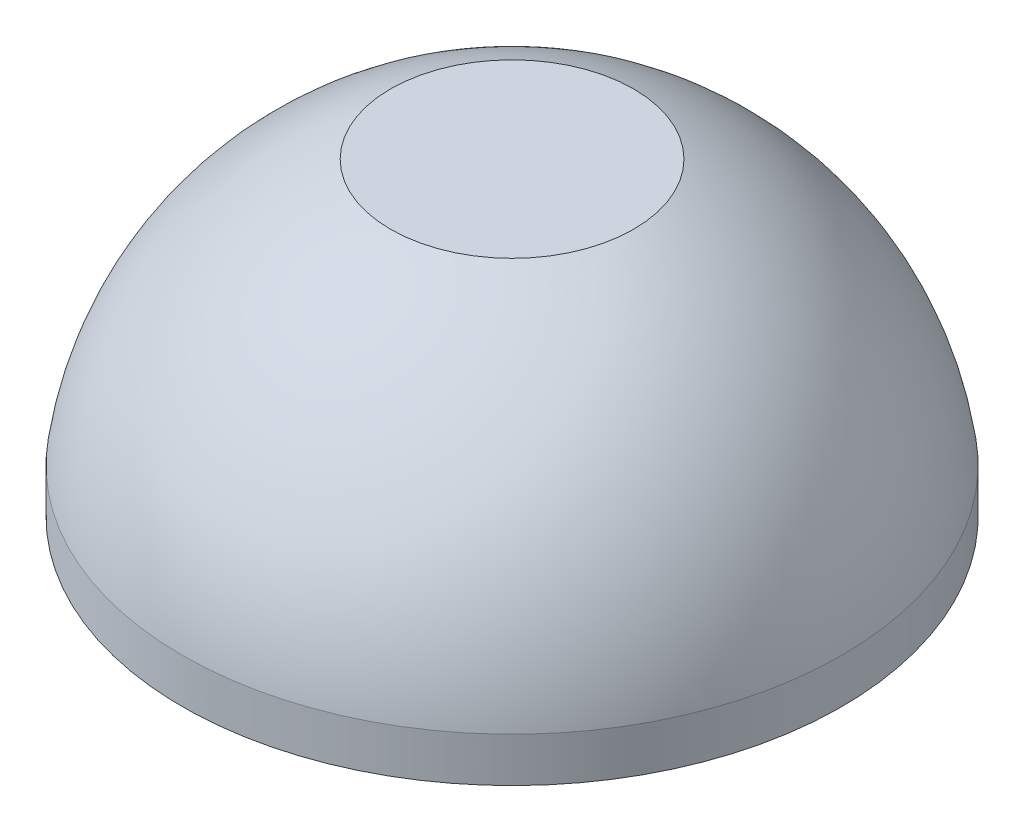
SolidWorks part; units mm, degrees
ref_plane "Front Plane" through (0, 0, 0) normal (0, 0, 1) x (1, 0, 0)
ref_plane "Top Plane" through (0, 0, 0) normal (0, 1, 0) x (1, 0, 0)
ref_plane "Right Plane" through (0, 0, 0) normal (1, 0, 0) x (0, 0, -1)
sketch "Sketch2" plane through (0, 0, 0) normal (0, 0, 1) x (1, 0, 0)
  line L0 (0, 70.1138) -> (-27.5371, 70.1138)
  line L1 (-74.65, 10.0805) -> (-74.65, 0)
  line L2 (-74.65, 0) -> (-69.65, 0)
  line L3 (-69.65, 0) -> (-69.65, 7.0805)
  line L4 (0, 68.7586) -> (-15, 68.7586)
  line L5 (-69.65, 10.0805) -> (-61.65, 10.0805)
  line L6 (-61.65, 10.0805) -> (-61.65, 6.207)
  line L7 (-64.65, 7.0805) -> (-69.65, 7.0805)
  line L8 (0, 70.1138) -> (0, 68.7586)
  line L9 (-61.65, 6.207) -> (-61.65, 0)
  line L10 (-61.65, 0) -> (-64.65, 0)
  line L11 (-64.65, 0) -> (-64.65, 7.0805)
  line L12 (0, -4.1047) -> (0, 42.6851) construction
  arc A0 (-27.5371, 70.1138) -> (-74.65, 10.0805) centre (0, 0) ccw
  arc A1 (-69.65, 10.0805) -> (-15, 68.7586) centre (0, 0) cw
  dimension "D1" = 15
  dimension "D2" = 69.65
  dimension "D3" = 5
  dimension "D4" = 3
  dimension "D5" = 5
  dimension "D6" = 3
revolve "Revolve2" add sketch "Sketch2" angle 360 about L12
thread "Thread1" pitch 5.08 start angle 0, offset 5, length 0, pitch 5.08, diameter 129.3
ref_plane "Plane1" through (64.65, -5, 0) normal (0, 0, 1) x (1, 0, 0)
sketch "Thread Profile1" plane through (64.65, -5, 0) normal (0, 0, 1) x (1, 0, 0)
  line L0 (0, 0) -> (0, 5.08) construction
  line L1 (0, 0) -> (0, 3.6346)
  line L2 (0.508, 3.6346) -> (1.524, 3.6346) construction
  line L3 (1.524, 2.1681) -> (1.524, 1.4665)
  line L4 (1.27, 2.6081) -> (0.254, 3.1946)
  line L5 (1.27, 1.0265) -> (0.254, 0.4399)
  line L6 (0.508, 0) -> (1.524, 0) construction
  arc A0 (0.254, 3.1946) -> (0, 3.6346) centre (0.508, 3.6346) cw
  arc A1 (0.254, 0.4399) -> (0, 0) centre (0.508, 0) ccw
  arc A2 (1.524, 1.4665) -> (1.27, 1.0265) centre (1.016, 1.4665) cw
  arc A3 (1.524, 2.1681) -> (1.27, 2.6081) centre (1.016, 2.1681) ccw
  point P10 (1.524, 2.4614)
  point P17 (1.524, 1.1732)
  point P18 (0, 3.3413)
  point P19 (0, 0.2933)
  point P20 (0, 0)
  dimension "RootFillet1" = 0.508
  dimension "RootFillet2" = 0.508
  dimension "CrestFillet2" = 0.508
  dimension "CrestFillet1" = 0.508
  dimension "Pitch" = 5.08
  dimension "Angle1" = 30
  dimension "Angle2" = 30
  dimension "a" = 3.048
  dimension "b" = 1.524
  dimension "c" = 1.2882
sketch "Sketch5" plane through (0, 0, 0) normal (0, -1, 0) x (1, 0, 0)
  circle A0 centre (0, 0) radius 104.1874
extrude "Cut-Extrude1" cut sketch "Sketch5" along normal blind 10
